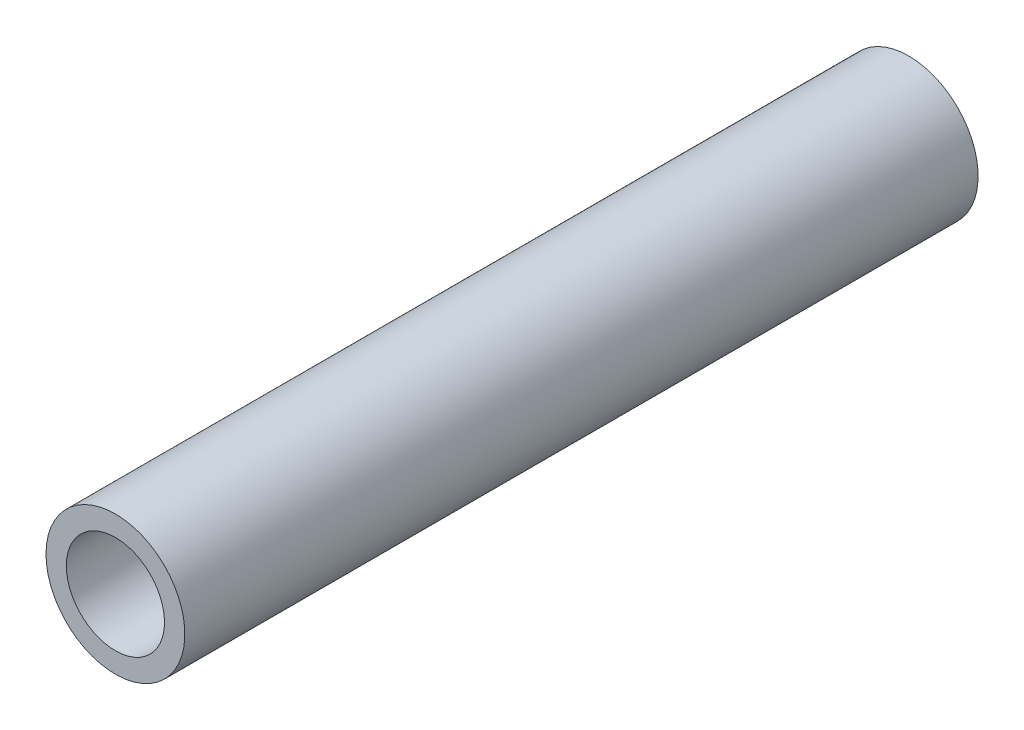
SolidWorks part; units mm, degrees
ref_plane "Front Plane" through (0, 0, 0) normal (0, 0, 1) x (1, 0, 0)
ref_plane "Top Plane" through (0, 0, 0) normal (0, 1, 0) x (1, 0, 0)
ref_plane "Right Plane" through (0, 0, 0) normal (1, 0, 0) x (0, 0, -1)
sketch "Sketch1" plane through (0, 0, 0) normal (0, 0, 1) x (1, 0, 0)
  circle A0 centre (0, 0) radius 13.335
  dimension "Pipe OD" = 26.67
extrude "Extrude-Thin1" add sketch "Sketch1" along normal mid plane 152.4 thin thin type one direction reverse wall 3.9116
